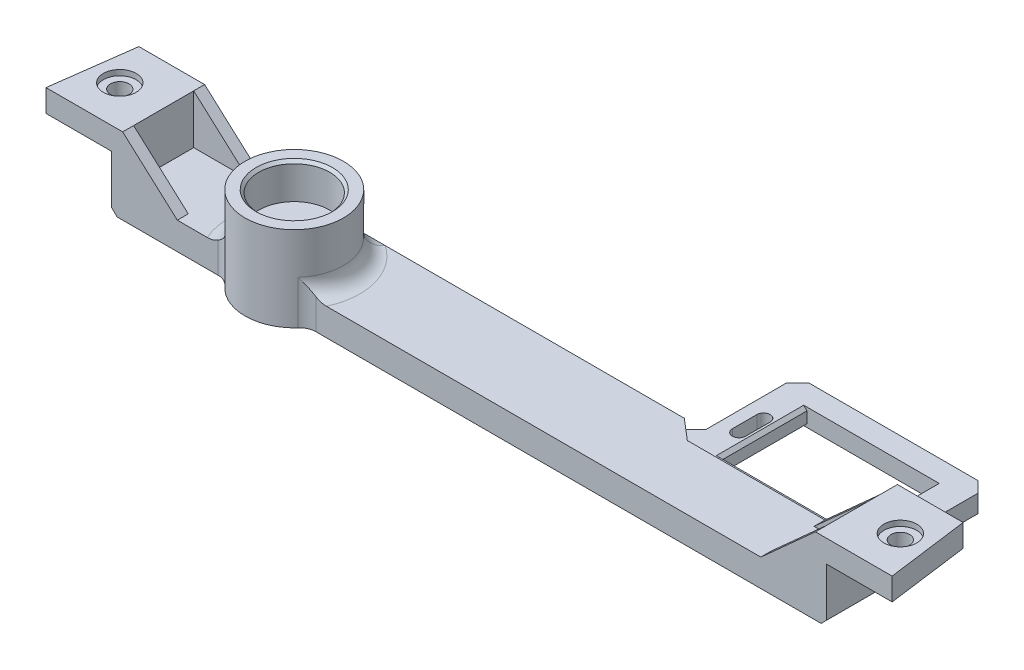
SolidWorks part; units mm, degrees
ref_plane "Plan de face" through (0, 0, 0) normal (0, 0, 1) x (1, 0, 0)
ref_plane "Plan de dessus" through (0, 0, 0) normal (0, 1, 0) x (1, 0, 0)
ref_plane "Plan de droite" through (0, 0, 0) normal (1, 0, 0) x (0, 0, -1)
sketch "Esquisse1" plane through (0, 0, 0) normal (0, 1, 0) x (1, 0, 0)
  line L1 (-65.435, -7.5) -> (65.435, -7.5)
  line L2 (-65.435, -7.5) -> (-65.435, 7.5)
  line L3 (-65.435, 7.5) -> (65.435, 7.5) construction
  line L4 (65.435, -7.5) -> (65.435, 7.5)
  line L5 (-65.435, -7.5) -> (65.435, 7.5) construction
  line L6 (-65.435, 7.5) -> (65.435, -7.5) construction
  line L13 (-65.435, 7.5) -> (65.435, 7.5)
  point P0 (0, 0)
  dimension "D1" = 130.87
  dimension "D2" = 15
extrude "Boss.-Extru.1" add sketch "Esquisse1" along normal blind 3.25
sketch "Esquisse2" plane through (0, 3.25, 0) normal (0, 1, 0) x (1, 0, 0)
  line L0 (65.435, 7.5) -> (-65.435, 7.5) construction
  line L1 (26.4, 26.25) -> (61.4, 26.25)
  line L2 (26.4, 26.25) -> (26.4, 7.5)
  line L3 (26.4, 7.5) -> (61.4, 7.5)
  line L4 (61.4, 26.25) -> (61.4, 7.5)
  line L5 (26.4, 26.25) -> (61.4, 7.5) construction
  line L6 (26.4, 7.5) -> (61.4, 26.25) construction
  point P0 (43.9, 16.875)
  dimension "D1" = 35
  dimension "D2" = 43.9
  dimension "D3" = 18.75
extrude "Boss.-Extru.3" add sketch "Esquisse2" against normal up to surface (3.25 mm away) up to face at (0, 0, 0)
sketch "Esquisse3" plane through (0, 3.25, 0) normal (0, 1, 0) x (1, 0, 0)
  line L0 (43.9, 26.25) -> (43.9, 14.25) construction
  line L1 (61.4, 26.25) -> (26.4, 26.25) construction
  line L3 (32.1, 6.25) -> (55.7, 6.25)
  line L4 (32.1, 6.25) -> (32.1, 22.25)
  line L5 (32.1, 22.25) -> (55.7, 22.25)
  line L6 (55.7, 6.25) -> (55.7, 22.25)
  line L7 (32.1, 6.25) -> (55.7, 22.25) construction
  line L8 (32.1, 22.25) -> (55.7, 6.25) construction
  dimension "D1" = 23.6
  dimension "D2" = 12
  dimension "D3" = 16
extrude "Enlèv. mat.-Extru.1" cut sketch "Esquisse3" against normal through all
chamfer "Chanfrein1" distance 2 angle 45 4 edges at (61.4, 1.625, -26.25) (61.4, 1.625, -7.5) (26.4, 1.625, -7.5) (26.4, 1.625, -26.25)
sketch "Esquisse4" plane through (0, 3.25, 0) normal (0, 1, 0) x (1, 0, 0)
  line L0 (43.9, 6.25) -> (43.9, 22.25) construction
  line L1 (32.1, 6.25) -> (55.7, 6.25) construction
  line L2 (55.7, 22.25) -> (32.1, 22.25) construction
  line L3 (43.9, 14.25) -> (57.9, 14.25) construction
  line L4 (57.9, 12) -> (57.9, 16.5) construction
  line L5 (56.7, 12) -> (56.7, 16.5)
  line L6 (59.1, 12) -> (59.1, 16.5)
  line L7 (29.9, 12) -> (29.9, 16.5) construction
  line L8 (31.1, 12) -> (31.1, 16.5)
  line L9 (28.7, 12) -> (28.7, 16.5)
  arc A0 (56.7, 12) -> (59.1, 12) centre (57.9, 12) ccw
  arc A1 (59.1, 16.5) -> (56.7, 16.5) centre (57.9, 16.5) ccw
  arc A2 (31.1, 12) -> (28.7, 12) centre (29.9, 12) cw
  arc A3 (28.7, 16.5) -> (31.1, 16.5) centre (29.9, 16.5) cw
  point P10 (57.9, 14.25)
  point P18 (29.9, 14.25)
  dimension "D2" = 1.2
  dimension "D1" = 14
  dimension "D3" = 4.5
extrude "Enlèv. mat.-Extru.2" cut sketch "Esquisse4" against normal through all
sketch "Esquisse5" plane through (0, 3.25, 0) normal (0, 1, 0) x (1, 0, 0)
  line L0 (65.435, -7.5) -> (65.435, 7.5)
  line L1 (65.435, 7.5) -> (63.4, 7.5)
  line L2 (63.4, 7.5) -> (59.6003, 4.25)
  line L3 (59.6003, 4.25) -> (28.1997, 4.25)
  line L4 (28.1997, 4.25) -> (24.4, 7.5)
  line L5 (24.4, 7.5) -> (-65.435, 7.5)
  line L6 (-65.435, 7.5) -> (-65.435, -7.5)
  line L7 (-65.435, -7.5) -> (65.435, -7.5)
  line L8 (43.9, 6.25) -> (43.9, 4.25) construction
  line L9 (32.1, 6.25) -> (55.7, 6.25) construction
  dimension "D1" = 2
  dimension "D2" = 5
extrude "Boss.-Extru.4" add sketch "Esquisse5" along normal blind 1.75
sketch "Esquisse6" plane through (0, 5, 0) normal (0, 1, 0) x (1, 0, 0)
  line L0 (-65.435, -7.5) -> (65.435, -7.5) construction
  circle A0 centre (-37, -2.5) radius 9
  dimension "D1" = 18
  dimension "D2" = 37
  dimension "D3" = 5
extrude "Boss.-Extru.5" add sketch "Esquisse6" along normal blind 10.55 and the other way up to surface (5 mm away) other way up to face at (57.9, 0, -14.25)
sketch "Esquisse7" plane through (0, 15.55, 0) normal (0, 1, 0) x (1, 0, 0)
  circle A0 centre (-37, -2.5) radius 6.5
  dimension "D1" = 13
extrude "Enlèv. mat.-Extru.3" cut sketch "Esquisse7" against normal blind 6.5
fillet "Congé1" radius 3 3 edges at (-29.5167, 2.5, 7.5) (-44.4833, 2.5, 7.5) (-37, 5, -6.5)
chamfer "Chanfrein2" distance 0.5 angle 45 1 edges at (-37, 15.55, 9)
sketch "Esquisse8" plane through (0, 5, 0) normal (0, 1, 0) x (1, 0, 0)
  line L0 (-26.0913, -7.5) -> (65.435, -7.5) construction
  line L1 (65.435, 7.5) -> (63.4, 7.5)
  line L2 (65.435, 7.5) -> (65.435, -7.5)
  line L3 (65.435, -7.5) -> (63.4, -7.5)
  line L4 (63.4, 7.5) -> (63.4, -7.5)
extrude "Boss.-Extru.6" add sketch "Esquisse8" along normal blind 9
sketch "Esquisse9" plane through (65.435, 0, 0) normal (1, 0, 0) x (0, 0, -1)
  line L0 (7.5, 14) -> (7.5, 0) construction
  line L1 (-7.5, 14) -> (7.5, 14)
  line L2 (-7.5, 14) -> (-7.5, 9.9)
  line L3 (-7.5, 9.9) -> (7.5, 9.9)
  line L4 (7.5, 14) -> (7.5, 9.9)
  line L5 (7.5, 5) -> (-7.5, 5) construction
  dimension "D1" = 4.9
extrude "Boss.-Extru.7" add sketch "Esquisse9" along normal blind 10
sketch "Esquisse10" plane through (0, 14, 0) normal (0, 1, 0) x (1, 0, 0)
  line L0 (75.435, 7.5) -> (77.435, -7.5)
  line L1 (77.435, -7.5) -> (75.435, -7.5)
  line L2 (75.435, -7.5) -> (75.435, 7.5)
  dimension "D1" = 2
extrude "Boss.-Extru.8" add sketch "Esquisse10" against normal up to surface (4.1 mm away) up to face at (70.435, 9.9, 0)
sketch "Esquisse16" plane through (0, 14, 0) normal (0, 1, 0) x (1, 0, 0)
  line L0 (71.435, 7.5) -> (71.435, -7.5) construction
  line L1 (63.4, -7.5) -> (77.435, -7.5) construction
  line L2 (75.435, 7.5) -> (63.4, 7.5) construction
  line L3 (65.435, -7.5) -> (65.435, 7.5) construction
  circle A0 centre (71.435, 0) radius 1.7
  dimension "D1" = 3.4
  dimension "D2" = 6
extrude "Enlèv. mat.-Extru.4" cut sketch "Esquisse16" against normal through all
sketch "Esquisse17" plane through (0, 14, 0) normal (0, 1, 0) x (1, 0, 0)
  circle A0 centre (71.435, 0) radius 3
  dimension "D1" = 6
extrude "Enlèv. mat.-Extru.5" cut sketch "Esquisse17" against normal blind 1
mirror "Symétrie1" about plane through (0, 0, 0) normal (1, 0, 0) of "Enlèv. mat.-Extru.5", "Enlèv. mat.-Extru.4", "Boss.-Extru.6", "Boss.-Extru.7", "Boss.-Extru.8"
sketch "Esquisse13" plane through (0, 0, 7.5) normal (0, 0, 1) x (1, 0, 0)
  line L0 (53.4, 5) -> (63.4, 14)
  line L1 (-26.0913, 5) -> (63.4, 5) construction
  line L2 (63.4, 14) -> (63.4, 5)
  line L3 (63.4, 5) -> (53.4, 5)
  line L4 (0, 0) -> (0, 27.3611) construction
  line L5 (-63.4, 5) -> (-53.4, 5)
  line L6 (-63.4, 14) -> (-63.4, 5)
  line L7 (-53.4, 5) -> (-63.4, 14)
  dimension "D1" = 10
extrude "Boss.-Extru.9" add sketch "Esquisse13" against normal blind 2
sketch "Esquisse14" plane through (0, 0, -4.25) normal (0, 0, -1) x (-1, 0, 0)
  line L0 (-63.4, 5) -> (-53.4, 5)
  line L1 (-59.6003, 5) -> (-28.1997, 5) construction
  line L2 (-53.4, 5) -> (-63.4, 14)
  line L3 (-63.4, 14) -> (-63.4, 5)
extrude "Boss.-Extru.10" add sketch "Esquisse14" against normal blind 2
sketch "Esquisse15" plane through (0, 0, -7.5) normal (0, 0, -1) x (-1, 0, 0)
  line L0 (53.4, 5) -> (63.4, 14)
  line L1 (43.6332, 5) -> (63.4, 5) construction
  line L2 (63.4, 14) -> (63.4, 5)
  line L3 (63.4, 5) -> (53.4, 5)
extrude "Boss.-Extru.11" add sketch "Esquisse15" against normal blind 2
chamfer "Chanfrein3" distance 1 angle 45 2 edges at (65.435, 0, 0) (-65.435, 0, 0)
chamfer "Chanfrein4" distance 0.6 angle 45 4 edges at (32.1, 0, -14.25) (55.7, 0, -14.25) (55.7, 3.25, -14.25) (32.1, 3.25, -14.25)
